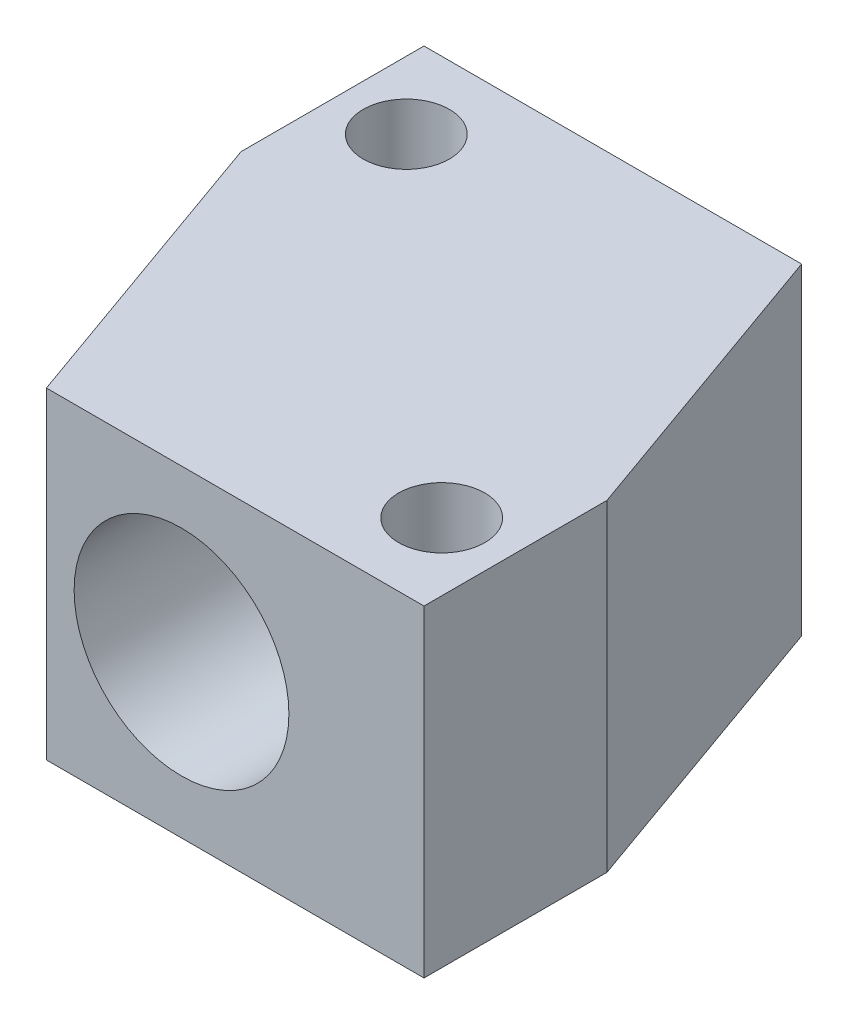
SolidWorks part; units mm, degrees
ref_plane "Front Plane" through (0, 0, 0) normal (0, 0, 1) x (1, 0, 0)
ref_plane "Top Plane" through (0, 0, 0) normal (0, 1, 0) x (1, 0, 0)
ref_plane "Right Plane" through (0, 0, 0) normal (1, 0, 0) x (0, 0, -1)
sketch "Sketch1" plane through (0, 0, 0) normal (0, 0, 1) x (1, 0, 0)
  line L1 (-36.13, 12) -> (36.13, 12)
  line L2 (-36.13, 12) -> (-36.13, -12)
  line L3 (-36.13, -12) -> (36.13, -12)
  line L4 (36.13, 12) -> (36.13, -12)
  line L5 (-36.13, 12) -> (36.13, -12) construction
  line L6 (-36.13, -12) -> (36.13, 12) construction
  point P0 (0, 0)
  dimension "D1" = 72.26
  dimension "D2" = 24
extrude "Boss-Extrude1" add sketch "Sketch1" along normal mid plane 72.26
sketch "Sketch2" plane through (0, 0, 36.13) normal (0, 0, 1) x (1, 0, 0)
  line L1 (-36.13, -12) -> (36.13, -12) construction
  line L2 (-16, -12) -> (16, -12)
  arc A0 (16, -12) -> (-16, -12) centre (0, -12) ccw
  dimension "D1" = 16
extrude "Cut-Extrude1" cut sketch "Sketch2" against normal through all
sketch "Sketch3" plane through (0, 12, 0) normal (0, 1, 0) x (1, 0, 0)
  line L0 (-36.13, -36.13) -> (-36.13, 36.13) construction
  line L2 (36.13, 36.13) -> (-36.13, 36.13) construction
  line L3 (0, 0) -> (-36.13, 0) construction
  line L4 (36.13, -36.13) -> (36.13, 36.13) construction
  line L5 (36.13, -36.13) -> (-36.13, -36.13) construction
  circle A0 centre (-26.0675, 23.43) radius 3.39
  circle A2 centre (26.0675, -23.43) radius 3.39
  dimension "D1" = 6.78
  dimension "D2" = 10.0625
  dimension "D6" = 6.78
  dimension "D3" = 10.0625
  dimension "D4" = 12.7
  dimension "D5" = 12.7
  dimension "D7" = 36.13
extrude "Cut-Extrude2" cut sketch "Sketch3" against normal through all
mirror "Mirror2" about plane through (-36.13, -12, 36.13) normal (0, 1, 0) of "Cut-Extrude2", "Boss-Extrude1", "Cut-Extrude1"
sketch "Sketch4" plane through (0, 12, 0) normal (0, 1, 0) x (1, 0, 0)
  line L0 (0, 0) -> (-36.13, 0) construction
  line L1 (36.13, -36.13) -> (36.13, 36.13) construction
  line L2 (36.13, 36.13) -> (-36.13, 36.13) construction
  line L3 (36.13, -36.13) -> (-36.13, -36.13) construction
  circle A0 centre (-26.0675, 23.43) radius 6.42
  circle A2 centre (26.0675, -23.43) radius 6.42
  dimension "D1" = 12.84
  dimension "D2" = 36.13
  dimension "D5" = 12.84
  dimension "D3" = 10.0625
  dimension "D4" = 12.7
extrude "Cut-Extrude3" cut sketch "Sketch4" against normal blind 10.42
sketch "Sketch5" plane through (0, 12, 0) normal (0, 1, 0) x (1, 0, 0)
  line L0 (-20.13, -36.13) -> (-36.13, 8.87)
  line L1 (36.13, -36.13) -> (-36.13, -36.13) construction
  line L2 (-36.13, -36.13) -> (-36.13, 36.13) construction
  line L3 (-36.13, 8.87) -> (-36.13, -36.13)
  line L4 (-36.13, -36.13) -> (-20.13, -36.13)
  line L5 (-36.13, 36.13) -> (36.13, -36.13) construction
  line L6 (36.13, 36.13) -> (36.13, -8.87)
  line L7 (36.13, 36.13) -> (-36.13, 36.13) construction
  line L8 (36.13, -36.13) -> (36.13, 36.13) construction
  line L9 (36.13, -8.87) -> (20.13, 36.13)
  line L10 (20.13, 36.13) -> (36.13, 36.13)
  dimension "D1" = 16
  dimension "D2" = 45
  dimension "D3" = 16
  dimension "D4" = 45
extrude "Cut-Extrude4" cut sketch "Sketch5" against normal through all
